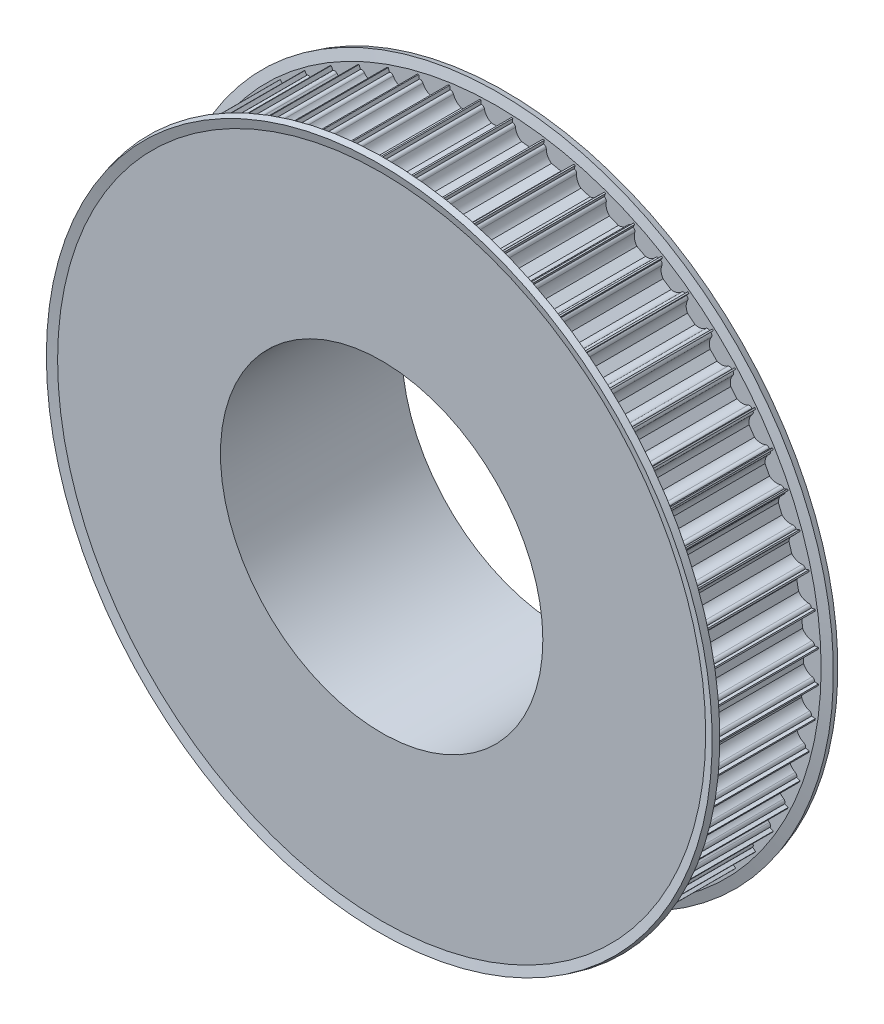
SolidWorks part; units mm, degrees
ref_plane "Front Plane" through (0, 0, 0) normal (0, 0, 1) x (1, 0, 0)
ref_plane "Top Plane" through (0, 0, 0) normal (0, 1, 0) x (1, 0, 0)
ref_plane "Right Plane" through (0, 0, 0) normal (1, 0, 0) x (0, 0, -1)
sketch "Sketch1" plane through (0, 0, 0) normal (1, 0, 0) x (0, 0, -1)
  line L0 (0, 0) -> (25.3151, 0) construction
  line L1 (0, 40) -> (45, 40)
  line L2 (45, 40) -> (45, 55.5)
  line L3 (45, 55.5) -> (30, 55.5)
  line L4 (30, 55.5) -> (30, 80)
  line L5 (30, 80) -> (0, 80)
  line L6 (0, 80) -> (0, 40)
  dimension "D1" = 40
  dimension "D2" = 80
  dimension "D3" = 30
  dimension "D4" = 15.5
  dimension "D5" = 45
  dimension "D6" = 15
revolve "Revolve1" add sketch "Sketch1" angle 360 about L0
sketch "Sketch5" plane through (0, 0, 0) normal (0, 0, 1) x (1, 0, 0)
  line L0 (-3.6742, 79) -> (-3.75, 79)
  line L1 (-3.75, 79) -> (-3.75, 81)
  line L2 (-3.75, 81) -> (3.75, 81)
  line L3 (3.75, 81) -> (3.75, 79)
  line L4 (3.75, 79) -> (3.6742, 79)
  line L6 (1.199, 76.25) -> (-1.199, 76.25)
  arc A0 (-2.9394, 78.4) -> (-1.199, 76.25) centre (0, 79) ccw
  arc A1 (-2.9394, 78.4) -> (-3.6742, 79) centre (-3.6742, 78.25) ccw
  arc A2 (2.9394, 78.4) -> (3.6742, 79) centre (3.6742, 78.25) cw
  arc A3 (1.199, 76.25) -> (2.9394, 78.4) centre (0, 79) ccw
  point P3 (0, 81)
  point P11 (-3, 79)
  point P14 (3, 79)
  dimension "D1" = 3
  dimension "D5" = 0.75
  dimension "D6" = 0.75
  dimension "D2" = 79
  dimension "D3" = 7.5
  dimension "D4" = 2
  dimension "D7" = 2.75
extrude "Cut-Extrude1" cut sketch "Sketch5" against normal up to next
pattern_circular "CirPattern1" count 64 over 360 about axis through (0, 0, 0) along (0, 0, 1) of "Cut-Extrude1"
sketch "Sketch6" plane through (0, 0, 0) normal (1, 0, 0) x (0, 0, -1)
  line L0 (15, -40.9775) -> (15, -13.6997) construction
  line L1 (30, -40.9775) -> (0, -40.9775) construction
  line L2 (30, -13.6997) -> (0, -13.6997) construction
  line L3 (30, 55.5) -> (30, 80.4056)
  line L4 (30, 80.4056) -> (30.5902, 82.6081)
  line L5 (30.5902, 82.6081) -> (29.0902, 83.01)
  line L6 (29.0902, 83.01) -> (28.4471, 80.61)
  line L7 (28.4471, 80.61) -> (28.4471, 55.5)
  line L8 (28.4471, 55.5) -> (30, 55.5)
  line L10 (45, 55.5) -> (30, 55.5) construction
  line L11 (1.5529, 55.5) -> (0, 55.5)
  line L12 (1.5529, 80.61) -> (1.5529, 55.5)
  line L13 (0, 55.5) -> (0, 80.4056)
  line L14 (0, 80.4056) -> (-0.5902, 82.6081)
  line L15 (-0.5902, 82.6081) -> (0.9098, 83.01)
  line L16 (0.9098, 83.01) -> (1.5529, 80.61)
  line L17 (0, 0) -> (-21.568, 0) construction
  dimension "D1" = 15
  dimension "D2" = 1.5
  dimension "D3" = 25.11
  dimension "D4" = 2.4
revolve "Revolve2" add sketch "Sketch6" angle 360 about L17
